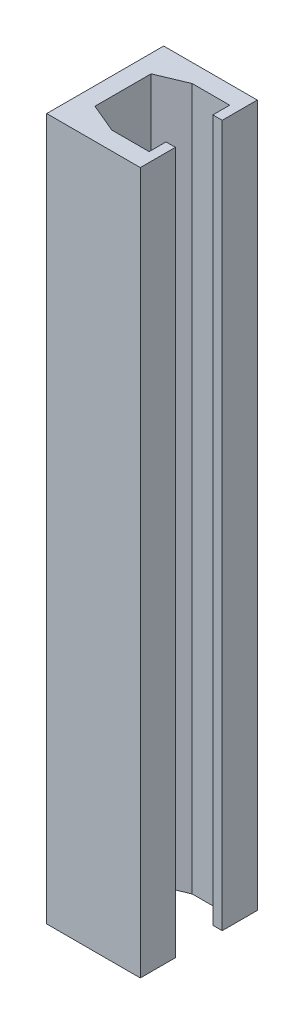
SolidWorks part; units mm, degrees
ref_plane "Front Plane" through (0, 0, 0) normal (0, 0, 1) x (1, 0, 0)
ref_plane "Top Plane" through (0, 0, 0) normal (0, 1, 0) x (1, 0, 0)
ref_plane "Right Plane" through (0, 0, 0) normal (1, 0, 0) x (0, 0, -1)
sketch "Sketch1" plane through (0, 0, 0) normal (0, 1, 0) x (1, 0, 0)
  line L1 (-10, -12.5) -> (10, -12.5)
  line L2 (-10, -12.5) -> (-10, 12.5)
  line L3 (-10, 12.5) -> (10, 12.5)
  line L4 (10, -12.5) -> (10, 12.5)
  line L7 (10, 0) -> (10, 5)
  line L8 (10, 5) -> (10, -5)
  line L9 (10, -5) -> (8, -5)
  line L11 (8, 5) -> (10, 5)
  line L13 (0, 8.6) -> (8, 8.6)
  line L14 (8, 8.6) -> (8, 5)
  line L16 (0, -8.6) -> (8, -8.6)
  line L17 (8, -8.6) -> (8, -5)
  line L18 (8, 8.6) -> (0, 8.6)
  line L22 (-6.2, 0) -> (-6.2, 6)
  line L23 (-6.2, 6) -> (-6.2, -6)
  line L24 (-6.2, -6) -> (0, -8.6)
  line L25 (0, 8.6) -> (-6.2, 6)
  line L27 (-6.2, 6) -> (-6.2, -6)
  point P0 (0, 0)
extrude "Boss-Extrude2" add sketch "Sketch1" along normal blind 150 contours L25 L13 L14 L11 L4 L3 L2 L1 L9 L17 L16 L24 L23 L22 region at (-9.6798, 0, 0)
